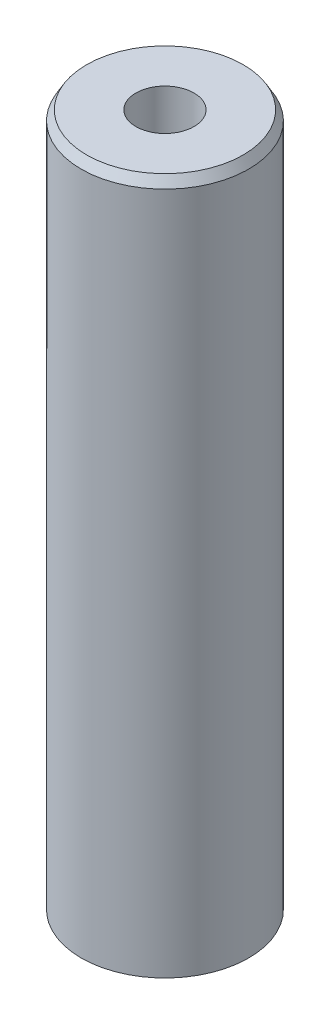
SolidWorks part; units mm, degrees
ref_plane "Front Plane" through (0, 0, 0) normal (0, 0, 1) x (1, 0, 0)
ref_plane "Top Plane" through (0, 0, 0) normal (0, 1, 0) x (1, 0, 0)
ref_plane "Right Plane" through (0, 0, 0) normal (1, 0, 0) x (0, 0, -1)
sketch "Sketch1" plane through (0, 0, 0) normal (0, 1, 0) x (1, 0, 0)
  circle A0 centre (0, 0) radius 20
  dimension "SHAFT_OD" = 40
extrude "Boss-Extrude1" add sketch "Sketch1" along normal blind 166.7039
sketch "Sketch2" plane through (0, 0, 0) normal (0, 1, 0) x (1, 0, 0)
  circle A0 centre (0, 0) radius 6.9453
  dimension "BORE_D" = 13.8907
extrude "Cut-Extrude1" cut sketch "Sketch2" along normal through all
chamfer "Chamfer1" distance 2.2719 angle 30 2 edges at (0, 166.7039, 20) (0, 0, 20) first distance on face at (0, 166.7039, 20) first distance on face at (0, 0, 6.9453)
